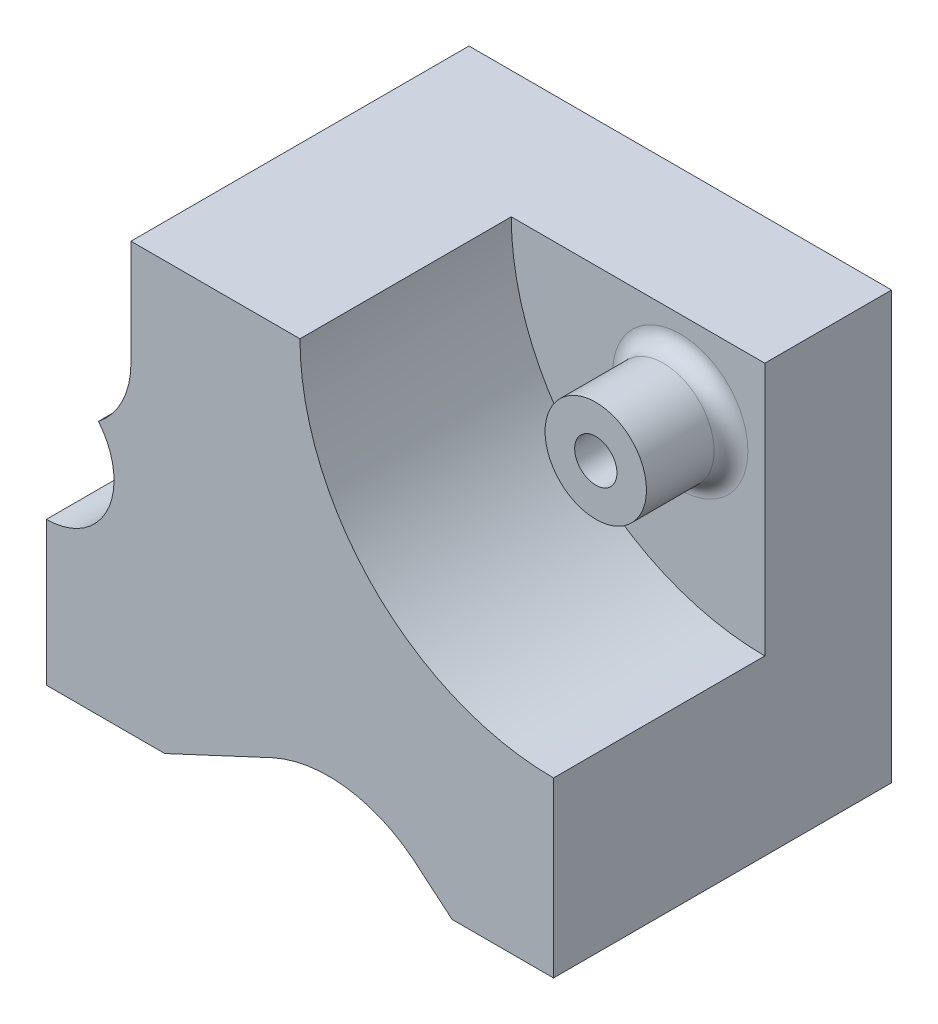
SolidWorks part; units mm, degrees
material "Alloy Steel"
ref_plane "Front Plane" through (0, 0, 0) normal (0, 0, 1) x (1, 0, 0)
ref_plane "Top Plane" through (0, 0, 0) normal (0, 1, 0) x (1, 0, 0)
ref_plane "Right Plane" through (0, 0, 0) normal (1, 0, 0) x (0, 0, -1)
sketch "Sketch1" plane through (0, 0, 0) normal (0, 0, 1) x (1, 0, 0)
  line L0 (0, 0) -> (-50, 0)
  line L1 (-50, 0) -> (-50, -12.5)
  line L2 (-50, -12.5) -> (-60, -12.5)
  line L3 (-60, -12.5) -> (-60, -50.5)
  line L4 (-60, -50.5) -> (-46, -50.5)
  line L5 (-46, -50.5) -> (-33.3117, -44.5833)
  line L6 (0, -50.5) -> (-12, -50.5)
  line L7 (-12, -50.5) -> (-16.5963, -46.6433)
  line L8 (0, -50.5) -> (0, 0)
  arc A0 (-16.5963, -46.6433) -> (-33.3117, -44.5833) centre (-26.618, -59.1159) ccw
  dimension "D12" = 16
  dimension "D1" = 50
  dimension "D2" = 10
  dimension "D3" = 38
  dimension "D4" = 12.5
  dimension "D5" = 50.5
  dimension "D6" = 14
  dimension "D7" = 25
  dimension "D8" = 12
  dimension "D9" = 40
  dimension "D10" = 14
  dimension "D11" = 6
extrude "Boss-Extrude1" add sketch "Sketch1" against normal blind 40
sketch "Sketch2" plane through (0, 0, 0) normal (0, 0, 1) x (1, 0, 0)
  line L0 (-50, -12.5) -> (-60, -12.5)
  line L1 (0, 0) -> (-50, 0) construction
  line L2 (0, -50.5) -> (0, 0) construction
  line L3 (-60, -12.5) -> (-60, -50.5) construction
  line L4 (-60, -50.5) -> (-46, -50.5) construction
  line L6 (-30, 0) -> (0, 0)
  line L7 (0, 0) -> (0, -30)
  line L8 (-60, -12.5) -> (-60, -33.5)
  arc A0 (-30, 0) -> (0, -30) centre (0, 0) ccw
  arc A1 (-50, -12.5) -> (-60, -22.5) centre (-60, -12.5) cw
  arc A2 (-60, -33.5) -> (-53.8492, -20.3846) centre (-60, -25.5) ccw construction
  arc A3 (-60, -33.5) -> (-53.8492, -20.3846) centre (-60, -25.5) ccw
  point P9 (-60, -33.5)
  line M1 (0, -50.5) -> (0, 0)
  line M2 (0, 0) -> (-50, 0)
  line M4 (-50, -12.5) -> (-60, -12.5)
  line M5 (-60, -12.5) -> (-60, -50.5)
  dimension "D1" = 30
  dimension "D3" = 8
  dimension "D2" = 17
extrude "Cut-Extrude1" cut sketch "Sketch2" against normal blind 25 contours A1 M4 M5 | A0 M2 M1 region at (-55.7559, -16.7441, 0) region at (-12.7324, -12.7324, 0)
extrude "Cut-Extrude2" cut sketch "Sketch2<7>" against normal blind 15 contours L8 A3 A1 region at (-56.3282, -26.9547, 0)
sketch "Sketch2<7>" plane through (0, 0, 0) normal (0, 0, 1) x (1, 0, 0) same geometry as "Sketch2"
sketch "Sketch3" plane through (0, 0, -25) normal (0, 0, 1) x (1, 0, 0)
  line L0 (0, -30) -> (0, 0) construction
  line L1 (0, 0) -> (-30, 0) construction
  circle A0 centre (-10, -10) radius 2.5
  circle A1 centre (-10, -10) radius 6
  dimension "D3" = 5
  dimension "D4" = 12
  dimension "D1" = 10
  dimension "D2" = 10
extrude "Cut-Extrude3" cut sketch "Sketch3" against normal through all contours A0
extrude "Boss-Extrude2" add sketch "Sketch3<6>" along normal blind 10
sketch "Sketch3<6>" plane through (0, 0, -25) normal (0, 0, 1) x (1, 0, 0) same geometry as "Sketch3"
fillet "Fillet2" radius 2 1 edges at (-4, -10, -25)
